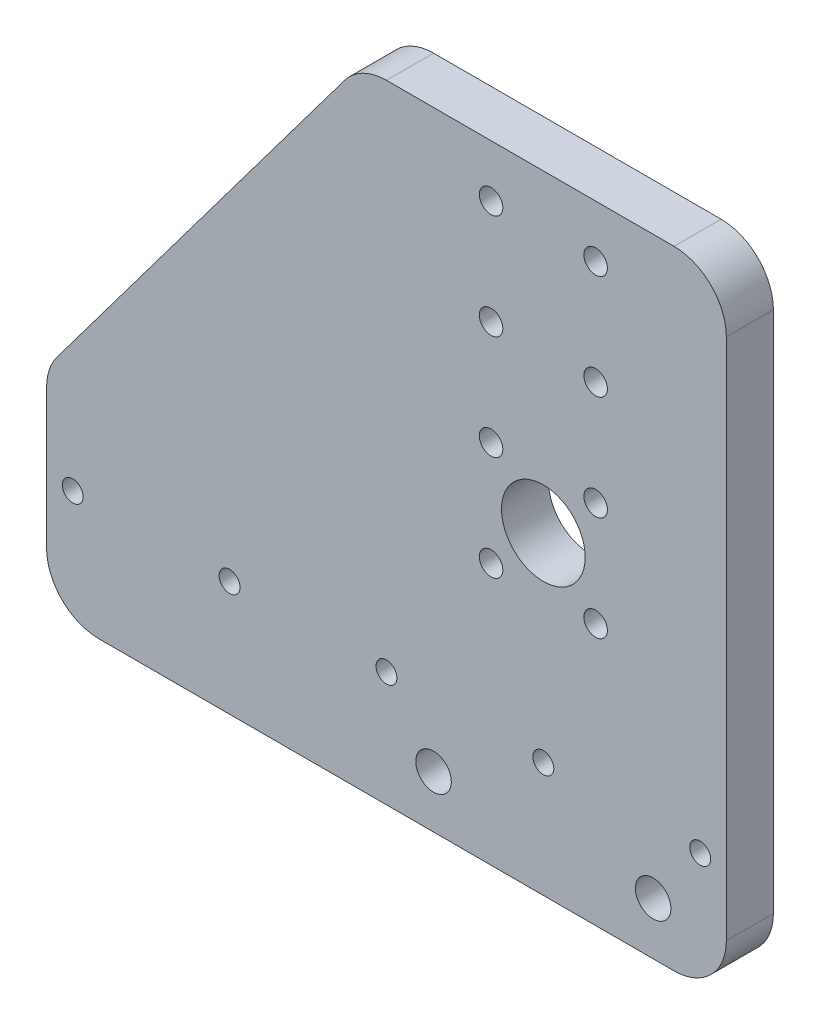
SolidWorks part; units mm, degrees
ref_plane "Front" through (0, 0, 0) normal (0, 0, 1) x (1, 0, 0)
ref_plane "Top" through (0, 0, 0) normal (0, 1, 0) x (1, 0, 0)
ref_plane "Right" through (0, 0, 0) normal (1, 0, 0) x (0, 0, -1)
sketch "Esquisse1" plane through (0, 0, 0) normal (0, 0, 1) x (1, 0, 0)
  line L0 (0, 0) -> (130, 0)
  line L1 (130, 0) -> (130, 120)
  line L2 (130, 120) -> (60, 120)
  line L3 (60, 120) -> (0, 40)
  line L4 (0, 40) -> (0, 0)
  dimension "D1" = 120
  dimension "D2" = 130
  dimension "D3" = 40
  dimension "D4" = 70
extrude "Boss.-Extru.1" add sketch "Esquisse1" along normal blind 9
sketch "Esquisse2" plane through (0, 0, 9) normal (0, 0, 1) x (1, 0, 0)
  line L0 (0, 22) -> (130, 22) construction
  line L1 (0, 40) -> (0, 0) construction
  line L2 (130, 0) -> (130, 120) construction
  line L3 (65, 22) -> (65, 26.8679) construction
  line L4 (0, 0) -> (130, 0) construction
  line L5 (95, 120) -> (95, 80) construction
  line L6 (130, 120) -> (60, 120) construction
  line L7 (95, 100) -> (92.3142, 100) construction
  line L8 (95, 80) -> (85.6936, 80) construction
  line L9 (95, 60) -> (92.3142, 60) construction
  circle A0 centre (65, 22) radius 2
  circle A1 centre (35, 22) radius 2
  circle A2 centre (5, 22) radius 2
  circle A3 centre (125, 22) radius 2
  circle A4 centre (95, 22) radius 2
  circle A5 centre (85, 110) radius 2.25
  circle A6 centre (85, 90) radius 2.25
  circle A7 centre (105, 90) radius 2.25
  circle A8 centre (105, 110) radius 2.25
  circle A9 centre (105, 50) radius 2.25
  circle A10 centre (105, 70) radius 2.25
  circle A11 centre (85, 70) radius 2.25
  circle A12 centre (85, 50) radius 2.25
  dimension "D1" = 4
  dimension "D2" = 30
  dimension "D3" = 30
  dimension "D6" = 20
  dimension "D7" = 10
  dimension "D8" = 4.5
  dimension "D4" = 22
  dimension "D5" = 20
extrude "Enlèv. mat.-Extru.1" cut sketch "Esquisse2" against normal through all
sketch "Esquisse3" plane through (0, 0, 9) normal (0, 0, 1) x (1, 0, 0)
  line L0 (85, 50) -> (105, 70) construction
  line L1 (95, 60) -> (95, 10) construction
  line L2 (95, 10) -> (74, 10) construction
  circle A0 centre (95, 60) radius 8
  circle A1 centre (74, 10) radius 3.4
  circle A2 centre (116, 10) radius 3.4
  dimension "D1" = 16
  dimension "D2" = 21
  dimension "D3" = 6.8
  dimension "D4" = 50
extrude "Enlèv. mat.-Extru.2" cut sketch "Esquisse3" against normal through all
fillet "Congé1" radius 10 5 edges at (0, 40, 4.5) (60, 120, 4.5) (130, 120, 4.5) (130, 0, 4.5) (0, 0, 4.5)
sketch "Esquisse5" [suppressed] plane through (0, 0, 0) normal (0, 0, -1) x (-1, 0, 0)
  line L0 (-95, 60) -> (-95, 81.9203) construction
  line L1 (-95, 60) -> (-116.9203, 60) construction
  line L2 (-95, 60) -> (-91.0893, 63.9107) construction
  line L3 (-95, 60) -> (-95, 38.0797) construction
  line L4 (-95, 60) -> (-73.0797, 60) construction
  circle A0 centre (-95, 81.9203) radius 1.5
  circle A1 centre (-116.9203, 60) radius 1.5
  circle A2 centre (-95, 38.0797) radius 1.5
  circle A3 centre (-73.0797, 60) radius 1.5
  dimension "D1" = 31
  dimension "D2" = 3
  dimension "D3" = 45
extrude "Enlèv. mat.-Extru.3" [suppressed] cut sketch "Esquisse5" against normal through all
